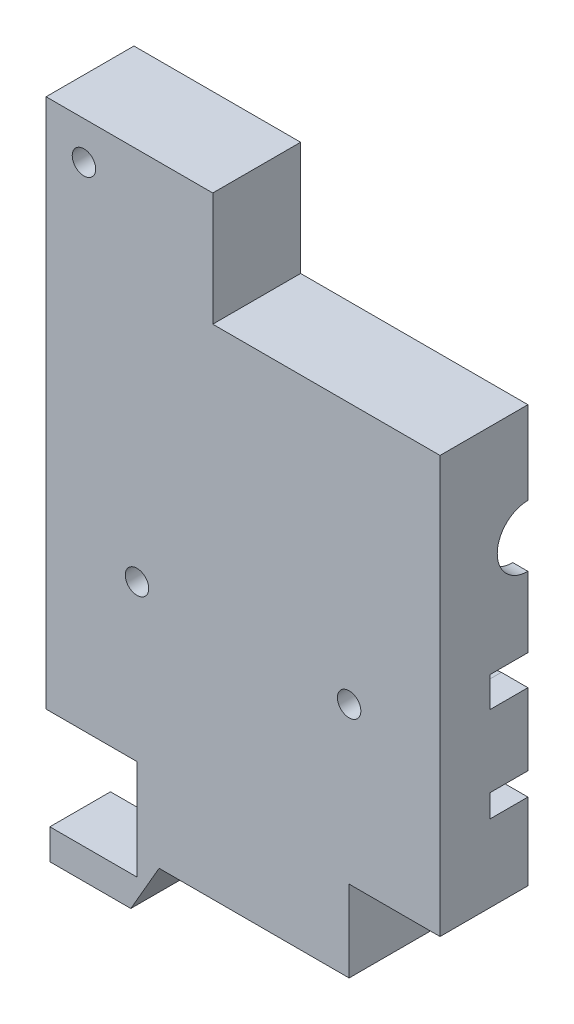
SolidWorks part; units mm, degrees
ref_plane "Alzado" through (0, 0, 0) normal (0, 0, 1) x (1, 0, 0)
ref_plane "Planta" through (0, 0, 0) normal (0, 1, 0) x (1, 0, 0)
ref_plane "Vista lateral" through (0, 0, 0) normal (1, 0, 0) x (0, 0, -1)
sketch "Croquis1" plane through (0, 0, 0) normal (0, 0, 1) x (1, 0, 0)
  line L0 (0, 0) -> (0, 90)
  line L1 (0, 90) -> (52, 90)
  line L2 (52, 90) -> (52, 0)
  line L3 (52, 0) -> (0, 0)
  dimension "D1" = 90
  dimension "D2" = 52
extrude "Saliente-Extruir1" add sketch "Croquis1" along normal blind 11.6
ref_plane "Plano1" through (50, 0, 0) normal (1, 0, 0) x (0, 0, -1)
sketch "Croquis2" plane through (50, 0, 0) normal (1, 0, 0) x (0, 0, -1)
  line L0 (0, 0) -> (0, 90) construction
  line L1 (0, 52.45) -> (0, 67.55)
  arc A0 (0, 67.55) -> (0, 52.45) centre (0, 60) ccw
  dimension "D1" = 15.1
  dimension "D2" = 30
extrude "Cortar-Extruir1" cut sketch "Croquis2" against normal blind 48
ref_plane "Plano2" through (38, 0, 0) normal (1, 0, 0) x (0, 0, -1)
sketch "Croquis3" plane through (38, 0, 0) normal (1, 0, 0) x (0, 0, -1)
  line L0 (0, 0) -> (0, 90) construction
  line L1 (0, 7.45) -> (0, 22.55)
  line L2 (-11.6, 90) -> (0, 90) construction
  arc A0 (0, 22.55) -> (0, 7.45) centre (0, 15) ccw
  dimension "D1" = 15.1
  dimension "D2" = 75
extrude "Cortar-Extruir2" cut sketch "Croquis3" against normal blind 24
sketch "Croquis4" plane through (52, 0, 0) normal (1, 0, 0) x (0, 0, -1)
  line L0 (0, 0) -> (0, 90) construction
  line L1 (0, 0) -> (0, 90)
  circle A0 centre (0, 60) radius 4.05
  dimension "D1" = 8.1
  dimension "D2" = 30
extrude "Cortar-Extruir3" cut sketch "Croquis4" against normal through all contours L1 A0 region at (52, 60, 1.7189)
sketch "Croquis5" plane through (52, 0, 0) normal (1, 0, 0) x (0, 0, -1)
  line L0 (0, 0) -> (0, 55.95) construction
  line L1 (0, 0) -> (0, 55.95)
  circle A0 centre (0, 15) radius 4.05
  dimension "D1" = 8.1
  dimension "D2" = 75
extrude "Cortar-Extruir4" cut sketch "Croquis5" against normal through all contours L1 A0 region at (52, 15, 1.7189)
sketch "Croquis6" plane through (0, 0, 0) normal (0, 0, -1) x (-1, 0, 0)
  line L10 (-2, 52.45) -> (-50, 52.45) construction
  line L13 (-2, 52.45) -> (-50, 52.45) construction
  line L18 (-2, 21.55) -> (-11.5, 21.55)
  line L19 (-11.5, 21.55) -> (-11.5, 25.05)
  line L20 (-11.5, 25.05) -> (-40.5, 25.05)
  line L21 (-2, 52.45) -> (-26, 52.45)
  line L22 (-40.5, 21.55) -> (-40.5, 25.05)
  line L23 (-40.5, 21.55) -> (-50, 21.55)
  line L24 (-26, 49.95) -> (-26, 22.55) construction
  line L25 (-2, 49.95) -> (-50, 49.95)
  line L26 (-50, 49.95) -> (-50, 21.55)
  line L27 (-2, 49.95) -> (-2, 21.55)
  line L28 (-52, 45.95) -> (-52, 48.45)
  point P1 (-6.75, 21.55)
  dimension "D2" = 9.5
  dimension "D3" = 2.5
  dimension "D4" = 9.5
  dimension "D5" = 24.9
  dimension "D6" = 28.4
  dimension "D7" = 9.5
  dimension "D8" = 3.5
  dimension "D9" = 3.5
  dimension "D10" = 9.5
extrude "Cortar-Extruir7" cut sketch "Croquis6" against normal blind 8 contours L27 L25 L26 L23 L22 L20 L19 L18 region at (26, 36.7516, 0)
sketch "Croquis7" plane through (0, 0, 8) normal (0, 0, -1) x (-1, 0, 0)
  line L0 (-2, 49.95) -> (-50, 49.95) construction
  line L3 (-50, 49.95) -> (-50, 21.55) construction
  circle A0 centre (-40, 40.55) radius 4
  dimension "D1" = 8
  dimension "D2" = 9.4
  dimension "D3" = 10
extrude "Saliente-Extruir2" add sketch "Croquis7" along normal blind 12
sketch "Croquis8" plane through (0, 0, 0) normal (0, 0, -1) x (-1, 0, 0)
  line L0 (-50, 49.95) -> (-50, 21.55) construction
  line L1 (-52, 19.05) -> (-52, 55.95) construction
  line L2 (-50, 46.65) -> (-50, 42.65)
  line L3 (-52, 42.65) -> (-52, 46.65)
  line L4 (-52, 46.65) -> (-50, 46.65)
  line L5 (-52, 42.65) -> (-50, 42.65)
  dimension "D1" = 4
  dimension "D2" = 3.3
extrude "Cortar-Extruir8" cut sketch "Croquis8" against normal blind 5
sketch "Croquis9" plane through (0, 0, 0) normal (0, 0, -1) x (-1, 0, 0)
  line L0 (-52, 42.65) -> (-48.4953, 42.65)
  line L1 (-46.4953, 40.65) -> (-46.4953, 37.65)
  line L2 (-46.4953, 37.65) -> (-52, 37.65)
  line L3 (-52, 19.05) -> (-52, 42.65) construction
  line L4 (-52, 37.65) -> (-52, 42.65)
  arc A0 (-46.4953, 40.65) -> (-48.4953, 42.65) centre (-48.4953, 40.65) ccw
  point P9 (-46.4953, 42.65)
  dimension "D3" = 2
  dimension "D1" = 5.5047
  dimension "D2" = 5
extrude "Saliente-Extruir4" add sketch "Croquis9" against normal blind 8
sketch "Croquis10" plane through (0, 0, -4) normal (0, 0, -1) x (-1, 0, 0)
  circle A0 centre (-40, 40.55) radius 4 construction
  circle A1 centre (-40, 40.55) radius 4
  circle A2 centre (-40, 40.55) radius 1.55
  dimension "D1" = 3.1
extrude "Cortar-Extruir9" cut sketch "Croquis10" against normal through all contours A2 region at (40, 40.55, -4)
sketch "Croquis11" plane through (0, 0, -4) normal (0, 0, -1) x (-1, 0, 0)
  circle A0 centre (-40, 40.55) radius 1.55 construction
  circle A1 centre (-40, 40.55) radius 1.55
  circle A2 centre (-40, 40.55) radius 2.8
  dimension "D1" = 5.6
extrude "Cortar-Extruir10" cut sketch "Croquis11" against normal blind 3
sketch "Croquis12" plane through (52, 0, 0) normal (1, 0, 0) x (0, 0, -1)
  line L0 (0, 19.05) -> (0, 42.65) construction
  line L1 (0, 30.15) -> (0, 33.15)
  line L2 (0, 33.15) -> (-5, 33.15)
  line L3 (-5, 33.15) -> (-5, 30.15)
  line L4 (-5, 30.15) -> (0, 30.15)
  dimension "D1" = 5
  dimension "D2" = 3
  dimension "D3" = 13.5
extrude "Cortar-Extruir11" cut sketch "Croquis12" against normal through all
sketch "Croquis13" plane through (0, 0, 0) normal (0, 0, -1) x (-1, 0, 0)
  line L0 (-52, 90) -> (-52, 75)
  line L2 (-52, 75) -> (-22, 75)
  line L3 (-22, 75) -> (-22, 90)
  line L4 (-52, 90) -> (0, 90) construction
  line L5 (-22, 90) -> (-52, 90)
  dimension "D1" = 30
  dimension "D2" = 15
extrude "Cortar-Extruir12" cut sketch "Croquis13" against normal blind 12
sketch "Croquis14" plane through (0, 0, 0) normal (0, 0, -1) x (-1, 0, 0)
  line L0 (-22, 90) -> (0, 90) construction
  line L1 (0, 90) -> (0, 64.05) construction
  circle A0 centre (-5, 85) radius 1.55
  circle A1 centre (-5, 85) radius 2.8
  dimension "D1" = 3.1
  dimension "D2" = 5.6
  dimension "D3" = 5
  dimension "D4" = 5
extrude "Cortar-Extruir13" cut sketch "Croquis14" against normal blind 12 contours A0 region at (5, 85, 0)
extrude "Cortar-Extruir14" cut sketch "Croquis14<3>" against normal blind 3
sketch "Croquis14<3>" plane through (0, 0, 0) normal (0, 0, -1) x (-1, 0, 0) same geometry as "Croquis14"
sketch "Croquis15" plane through (0, 0, 8) normal (0, 0, -1) x (-1, 0, 0)
  line L0 (-50, 30.15) -> (-2, 30.15)
  line L1 (-2, 30.15) -> (-2, 28.95)
  line L2 (-2, 30.15) -> (-2, 21.55) construction
  line L3 (-2, 28.95) -> (-50, 28.95)
  line L4 (-50, 30.15) -> (-50, 21.55) construction
  line L5 (-50, 28.95) -> (-50, 30.15)
  dimension "D1" = 1.2
extrude "Saliente-Extruir5" add sketch "Croquis15" along normal blind 8
sketch "Croquis16" plane through (0, 0, 0) normal (0, 0, -1) x (-1, 0, 0)
  line L0 (-52, 20) -> (-52, 0)
  line L2 (-52, 0) -> (-40, 0)
  line L3 (0, 0) -> (-52, 0) construction
  line L4 (-40, 0) -> (-40, 20)
  line L5 (-40, 20) -> (-52, 20)
  dimension "D1" = 20
  dimension "D2" = 12
extrude "Cortar-Extruir15" cut sketch "Croquis16" against normal through all
sketch "Croquis17" plane through (0, 0, 0) normal (0, 0, -1) x (-1, 0, 0)
  line L0 (0, 20) -> (-12, 20)
  line L1 (-12, 20) -> (-12, 0)
  line L2 (0, 0) -> (-40, 0) construction
  line L3 (-12, 0) -> (0, 0)
  line L4 (0, 0) -> (0, 20)
  dimension "D1" = 12
  dimension "D2" = 20
  dimension "D3" = 10.15
extrude "Cortar-Extruir16" cut sketch "Croquis17" against normal through all
sketch "Croquis18" plane through (0, 0, 11.6) normal (0, 0, 1) x (1, 0, 0)
  line L0 (0.5, 2.8) -> (12, 2.8)
  line L2 (0.5, 2.8) -> (0.5, 6.8)
  line L3 (0.5, 6.8) -> (12, 6.8)
  line L4 (12, 20) -> (12, 0) construction
  line L5 (12, 6.8) -> (12, 2.8)
  dimension "D1" = 4
  dimension "D2" = 2.8
  dimension "D3" = 11.5
extrude "Saliente-Extruir6" add sketch "Croquis18" against normal blind 8
sketch "Croquis19" plane through (0, 0, 8) normal (0, 0, -1) x (-1, 0, 0)
  line L0 (-2, 49.95) -> (-2, 33.15) construction
  line L1 (-2, 49.95) -> (-50, 49.95) construction
  circle A0 centre (-12, 40.55) radius 4
  dimension "D1" = 8
  dimension "D2" = 10
  dimension "D3" = 9.4
extrude "Saliente-Extruir7" add sketch "Croquis19" along normal up to surface (12 mm away) up to face at (37.2, 40.55, -4)
sketch "Croquis20" plane through (0, 0, -4) normal (0, 0, -1) x (-1, 0, 0)
  circle A0 centre (-12, 40.55) radius 4 construction
  circle A1 centre (-12, 40.55) radius 4
  circle A2 centre (-12, 40.55) radius 1.55
  circle A3 centre (-12, 40.55) radius 2.8
  dimension "D1" = 3.1
  dimension "D2" = 5.6
extrude "Cortar-Extruir17" cut sketch "Croquis20" against normal through all contours A2 region at (12, 40.55, -4)
extrude "Cortar-Extruir18" cut sketch "Croquis20<3>" against normal blind 3 contours A3 A2 region at (14.7208, 40.55, -4)
sketch "Croquis20<3>" plane through (0, 0, -4) normal (0, 0, -1) x (-1, 0, 0) same geometry as "Croquis20"
sketch "Croquis21" plane through (0, 0, 11.6) normal (0, 0, 1) x (1, 0, 0)
  line L0 (12, 2.8) -> (40, 2.8)
  line L1 (40, 0) -> (40, 20) construction
  line L2 (40, 2.8) -> (40, 0)
  line L3 (40, 0) -> (12, 0)
  line L4 (12, 2.8) -> (12, 0) construction
  line L5 (12, 0) -> (40, 0) construction
  line L6 (12, 0) -> (12, 2.8)
extrude "Cortar-Extruir19" cut sketch "Croquis21" against normal through all
sketch "Croquis22" plane through (0, 0, 11.6) normal (0, 0, 1) x (1, 0, 0)
  line L0 (0.5, 2.8) -> (40, 2.8) construction
  line L1 (11.1845, 2.8) -> (40, 2.8)
  line L2 (11.1845, 2.8) -> (14.9166, 9.2641)
  line L3 (14.9166, 9.2641) -> (40, 9.2641)
  line L4 (40, 2.8) -> (40, 20) construction
  line L5 (40, 2.8) -> (40, 9.2641)
  dimension "D1" = 25.0834
  dimension "D3" = 60
  dimension "D4" = 10.6845
extrude "Cortar-Extruir20" cut sketch "Croquis22" against normal through all
